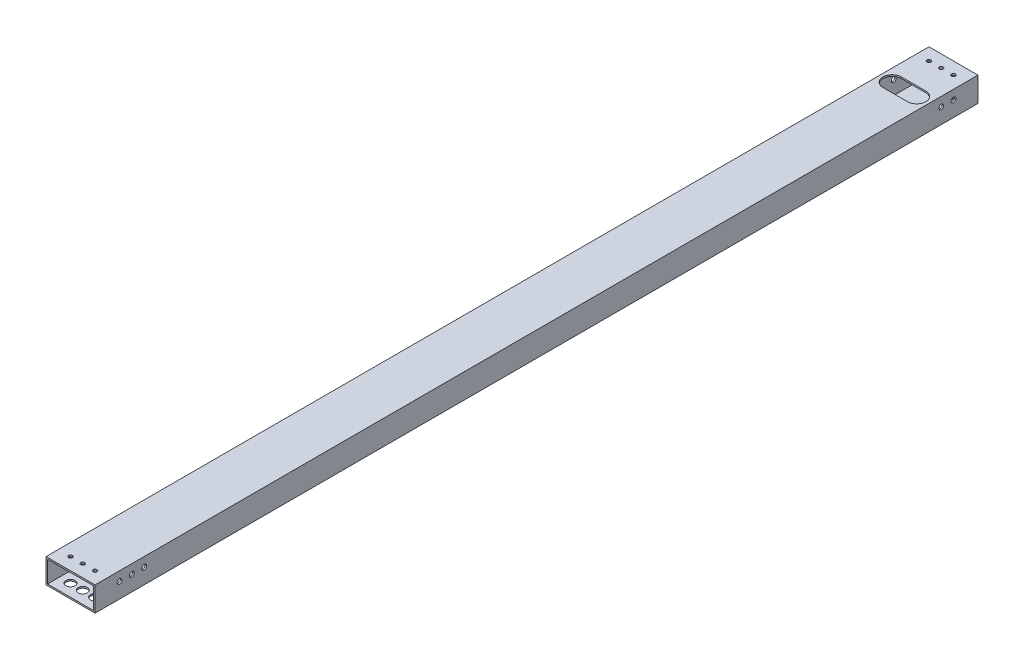
SolidWorks part; units mm, degrees
other "Markup1"
sketch "Sketch5" plane through (-25.4, -12.7, -457.2) normal (-0.35, -0.9329, -0.0852) x (-0.8023, 0.2515, 0.5413)
sketch "Sketch6" plane through (-25.4, -12.7, -457.2) normal (-0.35, -0.9329, -0.0852) x (-0.8023, 0.2515, 0.5413)
sketch "Sketch8" plane through (-25.4, -12.7, -457.2) normal (-0.35, -0.9329, -0.0852) x (-0.8023, 0.2515, 0.5413)
sketch "Sketch9" plane through (-25.4, -12.7, -457.2) normal (-0.35, -0.9329, -0.0852) x (-0.8023, 0.2515, 0.5413)
sketch "Sketch11" plane through (-25.4, -12.7, -457.2) normal (-0.35, -0.9329, -0.0852) x (-0.8023, 0.2515, 0.5413)
material "6061-T6 (SS)"
ref_plane "Front Plane" through (0, 0, 0) normal (0, 0, 1) x (1, 0, 0)
ref_plane "Top Plane" through (0, 0, 0) normal (0, 1, 0) x (1, 0, 0)
ref_plane "Right Plane" through (0, 0, 0) normal (1, 0, 0) x (0, 0, -1)
sketch "Sketch1" plane through (0, 0, 0) normal (0, 0, 1) x (1, 0, 0)
  line L0 (-23.8125, 11.1125) -> (23.8125, 11.1125)
  line L1 (-25.4, -12.7) -> (25.4, -12.7)
  line L2 (-25.4, -12.7) -> (-25.4, 12.7)
  line L3 (-25.4, 12.7) -> (25.4, 12.7)
  line L4 (25.4, -12.7) -> (25.4, 12.7)
  line L5 (-25.4, -12.7) -> (25.4, 12.7) construction
  line L6 (-25.4, 12.7) -> (25.4, -12.7) construction
  line L7 (23.8125, -11.1125) -> (23.8125, 11.1125)
  line L8 (-23.8125, -11.1125) -> (23.8125, -11.1125)
  line L9 (-23.8125, -11.1125) -> (-23.8125, 11.1125)
  point P0 (0, 0)
  dimension "D1" = 50.8
  dimension "D2" = 25.4
  dimension "D3" = 1.5875
extrude "Boss-Extrude1" add sketch "Sketch1" along normal mid plane 914.4
sketch "Sketch3" plane through (0, 12.7, 0) normal (0, 1, 0) x (1, 0, 0)
  line L2 (25.4, -457.2) -> (-25.4, -457.2) construction
  line L3 (25.4, 0) -> (-25.4, 0) construction
  line L4 (25.4, -457.2) -> (25.4, 457.2) construction
  line L5 (-25.4, -457.2) -> (-25.4, 457.2) construction
  circle A0 centre (0, -444.5) radius 2.0193
  circle A1 centre (12.7, -444.5) radius 2.0193
  circle A2 centre (-12.7, -444.5) radius 2.0193
  circle A3 centre (12.7, 444.5) radius 2.0193
  circle A4 centre (0, 444.5) radius 2.0193
  circle A5 centre (-12.7, 444.5) radius 2.0193
  dimension "D1" = 4.0386
  dimension "D2" = 12.7
  dimension "D3" = 12.7
  dimension "D4" = 12.7
extrude "Cut-Extrude2" cut sketch "Sketch3" against normal up to surface (1.5875 mm away) up to face at (0, 11.1125, 0)
sketch "Sketch4" plane through (0, -12.7, 0) normal (0, -1, 0) x (1, 0, 0)
  circle A0 centre (-12.7, 444.5) radius 2.0193 construction
  circle A1 centre (0, 444.5) radius 2.0193 construction
  circle A2 centre (12.7, 444.5) radius 2.0193 construction
  circle A3 centre (-12.7, 444.5) radius 2.0193
  circle A4 centre (0, 444.5) radius 2.0193
  circle A5 centre (12.7, 444.5) radius 2.0193
  circle A6 centre (-12.7, -444.5) radius 2.0193 construction
  circle A7 centre (0, -444.5) radius 2.0193 construction
  circle A8 centre (12.7, -444.5) radius 2.0193 construction
  circle A9 centre (-12.7, -444.5) radius 2.0193
  circle A10 centre (0, -444.5) radius 2.0193
  circle A11 centre (12.7, -444.5) radius 2.0193
  circle A12 centre (-12.7, 444.5) radius 4.7625
  circle A13 centre (0, 444.5) radius 4.7625
  circle A14 centre (12.7, 444.5) radius 4.7625
  circle A15 centre (-12.7, -444.5) radius 4.7625
  circle A16 centre (0, -444.5) radius 4.7625
  circle A17 centre (12.7, -444.5) radius 4.7625
  dimension "D1" = 9.525
  dimension "D2" = 9.525
extrude "Cut-Extrude4" cut sketch "Sketch4" against normal up to surface (1.5875 mm away) contours A12 A3 | A13 A4 | A4 | A3 | A5 | A14 A5 | A11 | A17 A11 | A16 A10 | A10 | A15 A9 | A9 region at (-12.7, -12.7, 444.5) region at (0, -12.7, 444.5) region at (12.7, -12.7, 444.5) region at (-12.7, -12.7, -444.5) region at (0, -12.7, -444.5) region at (12.7, -12.7, -444.5) region at (-17.3278, -12.7, 444.5) region at (-4.6278, -12.7, 444.5) region at (8.0722, -12.7, 444.5) region at (-17.3278, -12.7, -444.5) region at (-4.6278, -12.7, -444.5) region at (8.0722, -12.7, -444.5) up to face at (0, -11.1125, 0)
sketch "Sketch7" plane through (25.4, 0, 0) normal (1, 0, 0) x (0, 0, -1)
  line L0 (-457.2, -12.7) -> (-457.2, 12.7) construction
  line L1 (-457.2, 12.7) -> (457.2, 12.7) construction
  line L2 (0, 12.7) -> (0, -12.7) construction
  line L3 (-457.2, -12.7) -> (457.2, -12.7) construction
  circle A0 centre (-444.5, 3.175) radius 2.4892
  circle A1 centre (-431.8, 3.175) radius 2.4892
  circle A2 centre (-419.1, 3.175) radius 2.4892
  circle A3 centre (-406.4, 3.175) radius 2.4892
  circle A4 centre (406.4, 3.175) radius 2.4892
  circle A5 centre (419.1, 3.175) radius 2.4892
  circle A6 centre (431.8, 3.175) radius 2.4892
  circle A7 centre (444.5, 3.175) radius 2.4892
  dimension "D3" = 4.9784
  dimension "D1" = 12.7
  dimension "D2" = 9.525
  dimension "D4" = 12.7
  dimension "D5" = 12.7
  dimension "D6" = 12.7
extrude "Cut-Extrude5" cut sketch "Sketch7" against normal through all contours A5 | A6 | A1 | A2 | A3 region at (25.4, 3.175, 431.8) region at (25.4, 3.175, 419.1) region at (25.4, 3.175, 406.4) region at (25.4, 3.175, -419.1) region at (25.4, 3.175, -431.8)
sketch "Sketch10" plane through (0, 12.7, 0) normal (0, 1, 0) x (1, 0, 0)
  line L0 (25.4, 457.2) -> (-25.4, 457.2) construction
  circle A0 centre (-12.7, 406.4) radius 2.5527
  circle A1 centre (0, 406.4) radius 2.5527
  circle A2 centre (12.7, 406.4) radius 2.5527
  dimension "D1" = 5.1054
  dimension "D2" = 12.7
  dimension "D3" = 12.7
  dimension "D4" = 50.8
extrude "Cut-Extrude6" cut sketch "Sketch10" against normal through all
sketch "Sketch12" plane through (0, 12.7, 0) normal (0, 1, 0) x (1, 0, 0)
  line L0 (-12.7, 406.4) -> (12.7, 406.4) construction
  line L1 (-12.7, 415.925) -> (12.7, 415.925)
  line L2 (-12.7, 396.875) -> (12.7, 396.875)
  arc A0 (-12.7, 415.925) -> (-12.7, 396.875) centre (-12.7, 406.4) ccw
  arc A1 (12.7, 396.875) -> (12.7, 415.925) centre (12.7, 406.4) ccw
  point P4 (0, 406.4)
  dimension "D1" = 9.525
extrude "Cut-Extrude7" cut sketch "Sketch12" against normal up to surface (1.5875 mm away) up to face at (-10.1473, 11.1125, -406.4)
